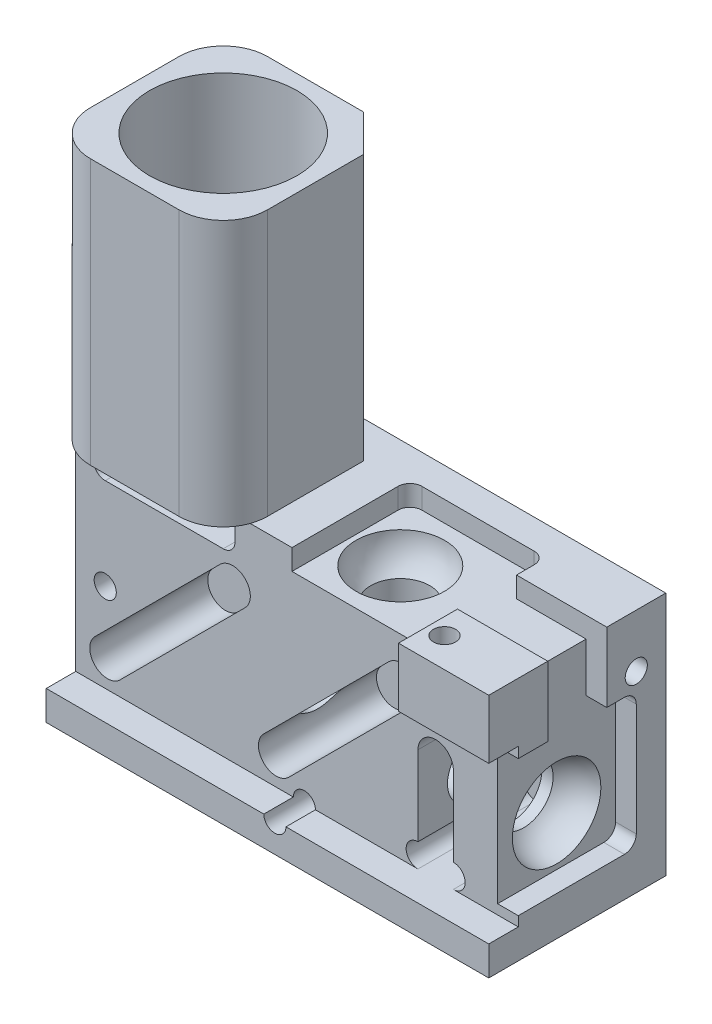
SolidWorks part; units mm, degrees
ref_plane "Front Plane" through (0, 0, 0) normal (0, 0, 1) x (1, 0, 0)
ref_plane "Top Plane" through (0, 0, 0) normal (0, 1, 0) x (1, 0, 0)
ref_plane "Right Plane" through (0, 0, 0) normal (1, 0, 0) x (0, 0, -1)
sketch "Sketch1" plane through (0, 0, 0) normal (0, 1, 0) x (1, 0, 0)
  line L1 (7.5, 3) -> (-7.5, 3)
  line L2 (7.5, 3) -> (7.5, -3)
  line L3 (7.5, -3) -> (-7.5, -3)
  line L4 (-7.5, 3) -> (-7.5, -3)
  line L5 (7.5, 3) -> (-7.5, -3) construction
  line L6 (7.5, -3) -> (-7.5, 3) construction
  point P0 (0, 0)
  dimension "D1" = 6
  dimension "D2" = 15
extrude "Main Body Ext" add sketch "Sketch1" along normal blind 8.3
sketch "Sketch8" plane through (0, 8.3, 0) normal (0, 1, 0) x (1, 0, 0)
  line L0 (-2.75, 3) -> (-1.5, 1.75)
  line L1 (-2.75, 3) -> (-7.5, 3)
  line L2 (-1.5, 1.75) -> (-1.5, -3)
  line L3 (-1.5, -3) -> (-7.5, -3)
  line L4 (-7.5, 3) -> (-7.5, -3)
  line L5 (-2.125, 2.375) -> (-7.5, -3) construction
  line L6 (-1.5, -3) -> (-7.5, 3) construction
  line L7 (-7.5, 3) -> (-7.5, -3) construction
  line L8 (0, 0) -> (-4.5, 0) construction
  point P0 (-4.5, 0)
  dimension "D1" = 6
  dimension "D2" = 6
  dimension "D3" = 1.25
  dimension "D4" = 3
extrude "Emission Path Ext" add sketch "Sketch8" along normal blind 9
sketch "Sketch3" plane through (0, 0, 0) normal (0, -1, 0) x (1, 0, 0)
  line L0 (-7.5, -3) -> (-7.5, 3) construction
  line L1 (0, 0) -> (-4.5, 0) construction
  circle A0 centre (-4.5, 0) radius 1.25
  dimension "D1" = 3
  dimension "D2" = 2.5
extrude "Emission and Grin Cut" cut sketch "Sketch3" against normal through all
sketch "Sketch4" plane through (7.5, 0, 0) normal (1, 0, 0) x (0, 0, -1)
  line L1 (-3, 0) -> (3, 0) construction
  circle A0 centre (0, 3) radius 1
  dimension "D1" = 2
  dimension "D2" = 3
extrude "Drum Lens Cut" cut sketch "Sketch4" against normal offset from surface (13 mm away) 2 up to face at (-7.5, 8.65, 0)
sketch "Sketch41" plane through (0, 8.3, 0) normal (0, 1, 0) x (1, 0, 0)
  line L1 (7.5, 3) -> (-2.75, 3) construction
  line L2 (-1.5, -3) -> (-1.5, 1.75) construction
  circle A0 centre (1.5, 0) radius 1
  dimension "D1" = 2
  dimension "D2" = 3
  dimension "D3" = 3
extrude "Addtl Light Source" cut sketch "Sketch41" against normal blind 5
sketch "Sketch5" plane through (0, 0, 3) normal (0, 0, 1) x (1, 0, 0)
  line L0 (-7.5, 0) -> (7.5, 0) construction
  line L1 (7.5, 8.3) -> (-7.5, 8.3)
  line L2 (7.5, 8.3) -> (7.5, 1)
  line L3 (7.5, 1) -> (-7.5, 1)
  line L4 (-7.5, 8.3) -> (-7.5, 1)
  line L5 (7.5, 8.3) -> (-7.5, 1) construction
  line L6 (7.5, 1) -> (-7.5, 8.3) construction
  line L7 (-1.5, 8.3) -> (7.5, 8.3) construction
  line L9 (7.5, 8.3) -> (7.5, 0) construction
  line L10 (-7.5, 17.3) -> (-7.5, 0) construction
  point P0 (0, 4.65)
  dimension "D1" = 1
extrude "FilterCover Cut1" cut sketch "Sketch5" against normal blind 1
sketch "Top-LED-Screw" plane through (0, 0, 2) normal (0, 0, 1) x (1, 0, 0)
  line L1 (7.5, 8.3) -> (4.44, 8.3)
  line L2 (7.5, 8.3) -> (7.5, 6.3)
  line L3 (7.5, 6.3) -> (4.44, 6.3)
  line L4 (4.44, 8.3) -> (4.44, 6.3)
  dimension "D1" = 2
  dimension "D2" = 3.06
extrude "Boss-Extrude1" add sketch "Top-LED-Screw" along normal blind 1
sketch "Sketch6" plane through (0, 0, 2) normal (0, 0, 1) x (1, 0, 0)
  line L0 (5.3, 4.5) -> (5.3, 1.8)
  line L1 (4.1, 4.5) -> (5.3, 4.5) construction
  line L2 (5.3, 1) -> (4.1, 1)
  line L3 (-7.5, 1) -> (7.5, 1) construction
  line L4 (-7.5, 8.3) -> (-7.5, 1) construction
  line L5 (-6.9, 7.9) -> (-6.9, 7.5)
  line L6 (4.1, 4.5) -> (4.1, 1.8)
  line L7 (-1.5, 8.3) -> (-7.5, 8.3) construction
  line L8 (-2.1, 7.9) -> (-2.1, 7.5)
  line L9 (-6, 1.5) -> (-6, 1) construction
  line L10 (-2.5, 8.3) -> (-6.5, 8.3)
  line L11 (-4.5, 3) -> (-4.5, 1) construction
  line L12 (-4.5, 3) -> (0.4851, 3) construction
  line L13 (-2.5, 7.1) -> (-6.5, 7.1)
  line L14 (-0.282, 1.5) -> (-0.282, 1) construction
  line L15 (-2.5, 8.3) -> (-6.5, 7.1) construction
  line L16 (-2.5, 7.1) -> (-6.5, 8.3) construction
  line L17 (4.1, 1.8) -> (5.3, 1.8) construction
  line L18 (-2.6059, 6.5912) -> (-6.8485, 2.3485)
  line L19 (7.5, 1) -> (7.5, 6.3) construction
  line L20 (-1.7574, 5.7426) -> (-6, 1.5)
  line L21 (-2.6059, 6.5912) -> (-6, 1.5) construction
  line L22 (-6.8485, 2.3485) -> (-1.7574, 5.7426) construction
  line L23 (1.826, 3.6081) -> (1.826, 1.6081) construction
  line L24 (1.826, 3.6081) -> (3.2165, 3.6081) construction
  line L25 (3.1121, 6.5912) -> (-1.1305, 2.3485)
  line L26 (3.9606, 5.7426) -> (-0.282, 1.5)
  line L27 (3.1121, 6.5912) -> (-0.282, 1.5) construction
  line L28 (-1.1305, 2.3485) -> (3.9606, 5.7426) construction
  line L33 (-2.5, 8.3) -> (1.102, 8.3) construction
  line L34 (1.102, 8.3) -> (1.102, 7.1) construction
  line L35 (1.102, 7.1) -> (-2.5, 7.1) construction
  line L36 (-6.5, 7.1) -> (-4.098, 7.1) construction
  line L37 (-4.098, 7.1) -> (-4.098, 8.3) construction
  line L38 (-4.098, 8.3) -> (-6.5, 8.3) construction
  line L39 (-6.5, 8.3) -> (-2.7284, 6.992) construction
  arc A0 (-2.5, 8.3) -> (-2.1, 7.9) centre (-2.5, 7.9) cw
  arc A1 (4.1, 4.5) -> (5.3, 4.5) centre (4.7, 4.5) cw
  arc A2 (-6.5, 8.3) -> (-6.9, 7.9) centre (-6.5, 7.9) ccw
  arc A3 (-2.6059, 6.5912) -> (-1.7574, 5.7426) centre (-2.1816, 6.1669) cw
  arc A4 (4.1, 1) -> (4.1, 1.8) centre (4.1, 1.4) cw
  arc A5 (-6.8485, 2.3485) -> (-6, 1.5) centre (-6.4243, 1.9243) ccw
  arc A6 (5.3, 1) -> (5.3, 1.8) centre (5.3, 1.4) ccw
  arc A7 (-6.5, 7.1) -> (-6.9, 7.5) centre (-6.5, 7.5) cw
  arc A8 (-2.5, 7.1) -> (-2.1, 7.5) centre (-2.5, 7.5) ccw
  arc A9 (3.1121, 6.5912) -> (3.9606, 5.7426) centre (3.5364, 6.1669) cw
  arc A10 (-1.1305, 2.3485) -> (-0.282, 1.5) centre (-0.7063, 1.9243) ccw
  point P5 (-4.5, 7.7)
  point P10 (-4.3029, 4.0456)
  point P21 (1.415, 4.0456)
  dimension "D10" = 0.5
  dimension "D5" = 2.2
  dimension "D8" = 0.4
  dimension "D11" = 0.4
  dimension "D12" = 0.4
  dimension "D1" = 1.2
  dimension "D2" = 45
  dimension "D3" = 3.5
  dimension "D4" = 1.2
  dimension "D6" = 2
  dimension "D7" = 4
  dimension "D9" = 3
  dimension "D13" = 1.2
  dimension "D14" = 3
  dimension "D15" = 6
  dimension "D16" = 45
  dimension "D17" = 0.5
  dimension "D18" = 1.2
  dimension "D19" = 2
  dimension "D20" = 6
extrude "FilterSet Cut2" cut sketch "Sketch6" against normal offset from surface (4 mm away) 1 up to face at (-0.0625, 9.2833, -3)
sketch "Sketch10" plane through (0, 17.3, 0) normal (0, 1, 0) x (1, 0, 0)
  line L0 (-4.5, 0) -> (-4.5, -3) construction
  line L1 (-7.5, -3) -> (-1.5, -3) construction
  line L3 (-4.5, 0) -> (-7.5, 0) construction
  line L4 (-7.5, 3) -> (-7.5, -3) construction
  circle A0 centre (-4.5, 0) radius 2.5
  dimension "D1" = 5
extrude "Emission Lens Cut" cut sketch "Sketch10" against normal offset from surface (8.5 mm away) 0.5 up to face at (-4.125, 8.3, 1.3125)
sketch "Sketch12" plane through (7.5, 0, 0) normal (1, 0, 0) x (0, 0, -1)
  line L0 (0, 3.635) -> (0, 0) construction
  line L1 (1.6, 5.94) -> (-1.6, 5.94)
  line L2 (1.6, 5.94) -> (1.6, 1.33) construction
  line L3 (-2, 1.33) -> (1.6, 1.33)
  line L4 (-1.6, 5.94) -> (-1.6, 1.33) construction
  line L5 (1.6, 5.94) -> (-1.6, 1.33) construction
  line L6 (1.6, 1.33) -> (-1.6, 5.94) construction
  line L7 (-3, 0) -> (3, 0) construction
  line L9 (-1.6, 5.94) -> (-2, 5.94)
  line L10 (-2, 1) -> (-2, 6.3) construction
  line L11 (-2, 5.94) -> (-2, 1.33)
  line L12 (2, 5.54) -> (2, 1.73)
  arc A1 (1.6, 5.94) -> (2, 5.54) centre (1.6, 5.54) cw
  arc A2 (1.6, 1.33) -> (2, 1.73) centre (1.6, 1.73) ccw
  circle A3 centre (0, 3) radius 1 construction
  point P0 (0, 3.635)
  dimension "D2" = 4.61
  dimension "D3" = 1.67
  dimension "D1" = 3.2
  dimension "D4" = 0.4
sketch "Sketch15" plane through (0, 0, 0) normal (0, -1, 0) x (1, 0, 0)
  line L0 (-6.25, 1.875) -> (-6.25, -1.875) construction
  line L2 (-1.5, 0) -> (-4.5, 0) construction
  line L3 (-4.5, 0) -> (-6.25, 0) construction
  circle A0 centre (-6.25, -1.875) radius 0.795
  circle A1 centre (-6.25, 1.875) radius 0.795
  circle A2 centre (-1.5, 0) radius 0.795
  dimension "D4" = 1.59
  dimension "D1" = 3.75
  dimension "D2" = 3
  dimension "D3" = 1.75
extrude "Magnets Cut" cut sketch "Sketch15" against normal blind 0.9
sketch "Sketch18" plane through (0, 0, 2) normal (0, 0, 1) x (1, 0, 0)
  line L0 (-7.5, 8.3) -> (-7.5, 1) construction
  line L1 (7.5, 1) -> (7.5, 6.3) construction
  line L2 (4.44, 8.3) -> (-1.5, 8.3) construction
  line L3 (-7.5, 0) -> (7.5, 0) construction
  line L7 (-7.5, 1) -> (4.1, 1) construction
  line L9 (-7.5, 1) -> (-7.5, 0) construction
  circle A0 centre (-6.5, 4) radius 0.375
  circle A1 centre (6, 5.8) radius 0.375
  circle A2 centre (0.25, 1) radius 0.375
  dimension "D1" = 0.75
  dimension "D2" = 1
  dimension "D3" = 2.5
  dimension "D4" = 1.5
  dimension "D5" = 3
  dimension "D6" = 1
  dimension "D7" = 7.75
extrude "Screw Holes Cut" cut sketch "Sketch18" against normal blind 2.5 and the other way through all
fillet "External Fillet 1" radius 1.5 2 edges at (-7.5, 8.65, -3)
sketch "Sketch28" plane through (0, 7.1, 0) normal (0, 1, 0) x (1, 0, 0)
  circle A0 centre (-4.5, 0) radius 1.5
  dimension "D1" = 3
extrude "Vertical-Path-Cut" cut sketch "Sketch28" against normal blind 4 and the other way through all
extrude "Cut-Extrude Original Light" cut sketch "Sketch12" against normal blind 0.7
sketch "Sketch44" plane through (0, 8.3, 0) normal (0, 1, 0) x (1, 0, 0)
  line L0 (-0.17, -2) -> (4.44, -2)
  line L1 (-0.17, -2) -> (-0.17, 1.6)
  line L2 (4.44, -2) -> (4.44, 1.6)
  line L3 (0.23, 2) -> (4.04, 2)
  line L6 (4.44, -2) -> (-1.5858, -2) construction
  circle A0 centre (1.5, 0) radius 1 construction
  arc A1 (4.44, 1.6) -> (4.04, 2) centre (4.04, 1.6) ccw
  arc A2 (-0.17, 1.6) -> (0.23, 2) centre (0.23, 1.6) cw
  point P10 (4.44, 2)
  point P13 (-0.17, 2)
  dimension "D3" = 1.67
  dimension "D4" = 0.4
  dimension "D5" = 0.4
  dimension "D1" = 4
  dimension "D2" = 4.61
extrude "Cut-Extrude Addtl Light" cut sketch "Sketch44" against normal blind 0.7
sketch "Sketch29" plane through (7.5, 0, 0) normal (1, 0, 0) x (0, 0, -1)
  line L0 (3, 8.3) -> (3, 0) construction
  line L1 (-3, 8.3) -> (3, 8.3) construction
  circle A0 centre (2, 6.5) radius 0.375
  circle A1 centre (0, 3) radius 1 construction
  dimension "D1" = 0.75
  dimension "D2" = 1
  dimension "D3" = 1.8
  dimension "D5" = 3.5
  dimension "D6" = 2
extrude "Side-LED-Screw" cut sketch "Sketch29" against normal blind 2.5
sketch "Sketch31" plane through (6.8, 0, 0) normal (1, 0, 0) x (0, 0, -1)
  circle A0 centre (0, 3) radius 1.6
  dimension "D1" = 3.2
sketch "Sketch32" plane through (7.5, 0, 0) normal (1, 0, 0) x (0, 0, -1)
  line L0 (-3, 8.3) -> (3, 8.3) construction
  line L1 (-1, 8.3) -> (1, 8.3)
  line L2 (-1, 8.3) -> (-1, 5.94)
  line L3 (-1, 5.94) -> (1, 5.94)
  line L4 (1, 8.3) -> (1, 5.94)
  line L5 (1.6, 5.94) -> (-2, 5.94) construction
  line L6 (-2, 5.94) -> (-2, 6.3) construction
  line L8 (3, 8.3) -> (3, 0) construction
  dimension "D1" = 1
  dimension "D2" = 2
extrude "Side-Wire-Slot-Cut" cut sketch "Sketch32" against normal up to surface (0.7 mm away) up to face at (6.8, 3.635, -0.5609)
sketch "Sketch45" plane through (0, 8.3, 0) normal (0, 1, 0) x (1, 0, 0)
  line L1 (4.44, -1) -> (6.8, -1)
  line L2 (4.44, -1) -> (4.44, 1)
  line L3 (4.44, 1) -> (6.8, 1)
  line L4 (6.8, -1) -> (6.8, 1)
  line L5 (4.44, -1) -> (6.8, 1) construction
  line L6 (4.44, 1) -> (6.8, -1) construction
  line L7 (6.8, 1) -> (6.8, -1) construction
  line L8 (4.44, -3) -> (4.44, 1.6) construction
  line L12 (6.8, -1) -> (7.5, -1) construction
  line L13 (6.8, 1) -> (7.5, 1) construction
extrude "Top-LED-slot" cut sketch "Sketch45" against normal blind 0.7
sketch "Sketch33" plane through (0, 0, 0) normal (0, 0, 1) x (1, 0, 0)
  line L0 (6.8, 3) -> (5.3, 3)
  line L1 (6.8, 1.4) -> (6.8, 4.6) construction
  line L2 (6.8, 3) -> (6.8, 4.5)
  arc A0 (5.3, 3) -> (6.8, 4.5) centre (6.8, 3) cw
  dimension "D2" = 1.5
revolve "Side-BallLens_Cut" cut sketch "Sketch33" angle 360 about L0
sketch "Sketch46" plane through (0, 7.6, 0) normal (0, 1, 0) x (1, 0, 0)
  circle A0 centre (1.5, 0) radius 1.5 construction
ref_plane "Plane1" through (1.5, 0, 0) normal (1, 0, 0) x (0, 0, -1)
sketch "Sketch47" plane through (1.5, 0, 0) normal (1, 0, 0) x (0, 0, -1)
  line L4 (-1.5, 7.6) -> (0, 7.6)
  line L5 (0, 7.6) -> (0, 6.1373)
  line L6 (1, 7.6) -> (-1, 7.6) construction
  arc A0 (0, 6.1373) -> (-1.5, 7.6) centre (0, 7.6378) cw
revolve "Top-BallLens_Cut" cut sketch "Sketch47" angle 360 about L5
sketch "Sketch36" plane through (0, 17.3, 0) normal (0, 1, 0) x (1, 0, 0)
  line L0 (-7.5, -1.5) -> (-7.5, -3)
  line L1 (-7.5, 1.5) -> (-7.5, -3) construction
  line L2 (-7.5, -3) -> (-6, -3)
  line L3 (-7.5, -3) -> (-3, -3) construction
  arc A0 (-7.5, -1.5) -> (-6, -3) centre (-6, -1.5) ccw
  dimension "D1" = 1.5
  dimension "D2" = 1.5
extrude "Cut-Extrude16" cut sketch "Sketch36" against normal up to surface (9 mm away) up to face at (-4.3971, 8.3, 1.2781)
sketch "Sketch37" plane through (0, 8.8, 0) normal (0, 1, 0) x (1, 0, 0)
  circle A0 centre (-4.5, 0) radius 2
  circle A1 centre (-4.5, 0) radius 1.5 construction
  dimension "D1" = 4
extrude "Cut-Extrude17" cut sketch "Sketch37" against normal up to next
sketch "Sketch51" plane through (0, 8.3, 0) normal (0, 1, 0) x (1, 0, 0)
  circle A0 centre (5, -2) radius 0.375
  circle A1 centre (1.5, 0) radius 1.5 construction
  dimension "D1" = 0.75
  dimension "D2" = 3.5
  dimension "D3" = 2
extrude "Top-LE-Screw" cut sketch "Sketch51" against normal blind 2.1
sketch "Notch" plane through (0, 0, 0) normal (0, -1, 0) x (1, 0, 0)
  line L0 (4.1286, -3) -> (3, -2.2476) construction
  line L1 (7.5, -3) -> (-6, -3) construction
  line L2 (3, -2.2476) -> (2.5865, -2.2476) construction
  line L3 (2.5865, -2.2476) -> (2.0849, -3) construction
  line L4 (3, -2.2476) -> (4.0396, -2.9406) construction
  line L5 (3, -2.2476) -> (2, -2.2476) construction
  line L6 (1.6849, -1.8476) -> (1.6849, -3)
  line L7 (4.8497, -3) -> (3.1211, -1.8476)
  line L8 (3.1211, -1.8476) -> (1.6849, -1.8476)
  line L9 (1.6849, -1.8476) -> (0.85, -3.1)
  line L10 (4.8497, -3) -> (1.6849, -3)
  line L12 (4.0396, -2.9406) -> (2.6528, -5.0208) construction
  line L13 (2.0849, -3) -> (2.0849, -2.2476) construction
  line L14 (2.0849, -2.2476) -> (2.5865, -2.2476) construction
  line M13 (-6, -3) -> (7.5, -3)
  dimension "D1" = 0.4
  dimension "D2" = 0.4
  dimension "D3" = 0.4
extrude "Notch-Extrude" cut sketch "Notch" against normal blind 2 contours L7 L8 L6 M13 | L6 L9 M13 region at (2.8893, 0, -2.496) region at (1.4288, 0, -2.6159)
